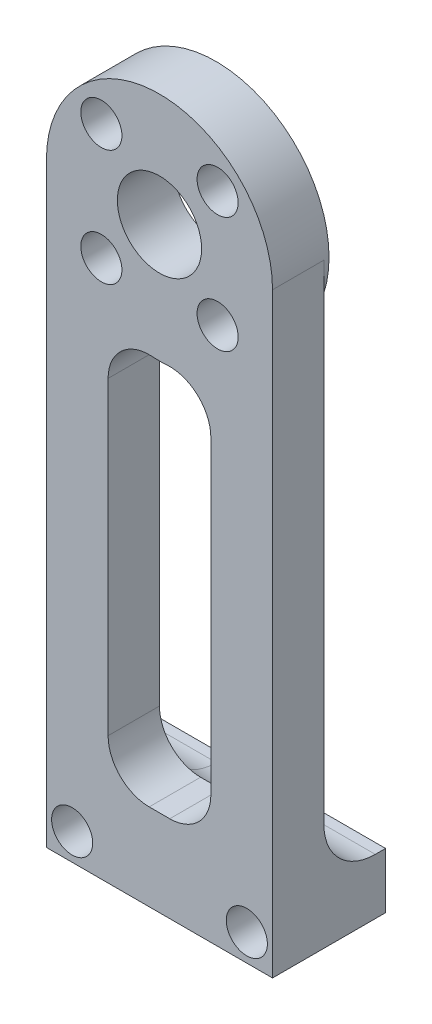
SolidWorks part; units mm, degrees
ref_plane "Front Plane" through (0, 0, 0) normal (0, 0, 1) x (1, 0, 0)
ref_plane "Top Plane" through (0, 0, 0) normal (0, 1, 0) x (1, 0, 0)
ref_plane "Right Plane" through (0, 0, 0) normal (1, 0, 0) x (0, 0, -1)
sketch "Sketch1" plane through (0, 0, 0) normal (0, 0, 1) x (1, 0, 0)
  line L0 (0, 29) -> (0, -29) construction
  line L2 (11, 29) -> (11, -29)
  line L4 (-11, 29) -> (-11, -29)
  line L5 (-11, -29) -> (11, -29)
  line L7 (11, -29) -> (-11, -29)
  line L8 (11, -29) -> (11, -23.58)
  line L9 (11, -23.58) -> (-11, -23.58)
  line L10 (-11, -29) -> (-11, -23.58)
  line L12 (-5, 18.6438) -> (-5, -20.58)
  line L13 (-5, -20.58) -> (5, -20.58)
  line L14 (5, 18.6438) -> (5, -20.58)
  circle A0 centre (0, 29) radius 11
  arc A1 (-5, 18.6438) -> (5, 18.6438) centre (0, 29) ccw
  point P0 (0, 0)
  point P2 (0, 0)
  point P8 (0, -29)
  dimension "D3" = 22
  dimension "D1" = 58
  dimension "D4" = 5.42
  dimension "D5" = 23
  dimension "D7" = 6
  dimension "D2" = 22
  dimension "D6" = 3
  dimension "D8" = 6
extrude "Boss-Extrude1" add sketch "Sketch1" along normal blind 5 contours L2 A0 L4 | A0 | A0 L0 L2 | L8 L7 L10 L9 region at (0, 29, 0) region at (10.43, 2.71, 0)
extrude "Boss-Extrude2" add sketch "Sketch1<3>" against normal blind 0.5 contours A0 region at (0, 29, 0)
sketch "Sketch1<3>" plane through (0, 0, 0) normal (0, 0, 1) x (1, 0, 0) same geometry as "Sketch1"
sketch "Sketch2" plane through (0, 0, 5) normal (0, 0, 1) x (1, 0, 0)
  line L0 (0, 29) -> (5.6569, 34.6569) construction
  line L1 (11, 29) -> (11, -29) construction
  circle A0 centre (0, 29) radius 4.1
  circle A1 centre (5.6569, 34.6569) radius 1.1
  circle A2 centre (5.6569, 34.6569) radius 2
  dimension "D1" = 8.2
  dimension "D2" = 2.2
  dimension "D5" = 4
  dimension "D3" = 8
  dimension "D4" = 45
extrude "Cut-Extrude1" cut sketch "Sketch2" against normal up to surface (5.5 mm away) contours A0 | A1 region at (0, 29, 5) region at (5.6569, 34.6569, 5) up to face at (11, 29, -0.5)
extrude "Cut-Extrude2" cut sketch "Sketch2<3>" against normal offset from surface (4.5 mm away) 1 contours A2 A1 region at (3.7134, 34.6569, 5) up to face at (4.1, 29, -0.5)
sketch "Sketch2<3>" plane through (0, 0, 5) normal (0, 0, 1) x (1, 0, 0) same geometry as "Sketch2"
pattern_circular "CirPattern2" count 4 over 360 about axis through (0, 29, 5) along (0, 0, 1) of "Cut-Extrude2", "Cut-Extrude1"
extrude "Boss-Extrude3" add sketch "Sketch1<6>" against normal blind 6 contours L0 L9 L4 L5 | L9 L0 L7 L2 region at (-5.5, -26.29, 0) region at (5.5, -26.29, 0)
sketch "Sketch1<6>" plane through (0, 0, 0) normal (0, 0, 1) x (1, 0, 0) same geometry as "Sketch1"
sketch "Sketch3" plane through (0, 0, 5) normal (0, 0, 1) x (1, 0, 0)
  line L0 (-8.5, -26.3852) -> (8.5, -26.3852) construction
  line L1 (-11, -29) -> (11, -29) construction
  circle A0 centre (-8.5, -26.3852) radius 1.1
  circle A1 centre (8.5, -26.3852) radius 1.1
  circle A2 centre (-8.5, -26.3852) radius 2
  circle A3 centre (8.5, -26.3852) radius 2
  point P4 (0, -26.3852)
  dimension "D1" = 2.2
  dimension "D4" = 4
  dimension "D2" = 17
  dimension "D3" = 2.6148
extrude "Cut-Extrude3" cut sketch "Sketch3" against normal up to surface (11 mm away) contours A0 | A1 region at (-8.5, -26.3852, 5) region at (8.5, -26.3852, 5) up to face at (0, -26.29, -6)
extrude "Cut-Extrude4" cut sketch "Sketch3<3>" against normal offset from surface (10 mm away) 1 up to face at (-7.4, -26.3852, -6)
sketch "Sketch3<3>" plane through (0, 0, 5) normal (0, 0, 1) x (1, 0, 0) same geometry as "Sketch3"
fillet "Filete1" radius 4 4 edges at (5, 18.6438, 2.5) (-5, 18.6438, 2.5) (5, -20.58, 2.5) (-5, -20.58, 2.5)
fillet "Filete3" radius 5 1 edges at (0, -23.58, 0)
move or copy body "Corpo-Mover/Copiar1" [suppressed] bodies to move or copy 117
